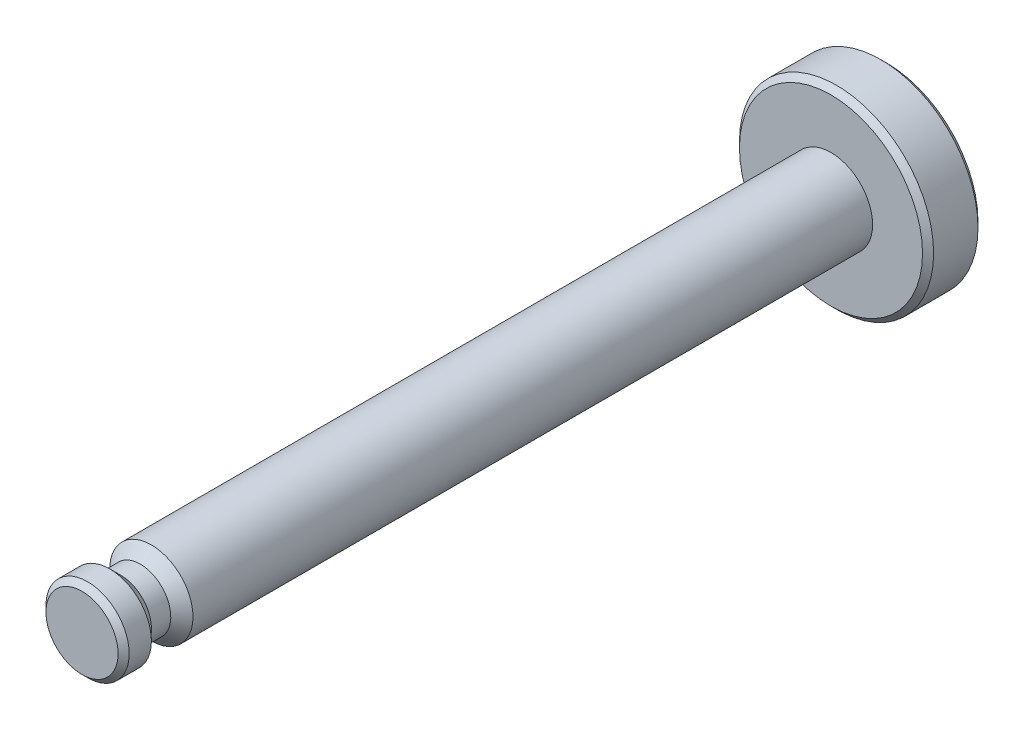
SolidWorks part; units mm, degrees
ref_plane "Front" through (0, 0, 0) normal (0, 0, 1) x (1, 0, 0)
ref_plane "Top" through (0, 0, 0) normal (0, 1, 0) x (1, 0, 0)
ref_plane "Right" through (0, 0, 0) normal (1, 0, 0) x (0, 0, -1)
sketch "Sketch2" plane through (0, 0, 0) normal (0, 0, 1) x (1, 0, 0)
  circle A0 centre (0, 0) radius 1.5
  dimension "D1" = 3
extrude "Shaft" add sketch "Sketch2" along normal blind 27
sketch "Sketch3" plane through (0, 0, 0) normal (0, 0, -1) x (-1, 0, 0)
  circle A3 centre (0, 0) radius 3.5
  dimension "D1" = 7
extrude "Head" add sketch "Sketch3" along normal blind 2
sketch "Sketch4" plane through (0, 0, 0) normal (1, 0, 0) x (0, 0, -1)
  line L0 (0, 0) -> (-25.25, 0) construction
  line L1 (-25.25, 0) -> (-25.25, 4.3666) construction
  line L2 (-26, 1.5) -> (-24.5, 1.5)
  line L3 (0, 1.5) -> (-27, 1.5) construction
  line L6 (-24.5, 1.5) -> (-24.9, 1.1)
  line L7 (-24.9, 1.1) -> (-25.6, 1.1)
  line L8 (-25.6, 1.1) -> (-26, 1.5)
  dimension "D1" = 25.25
  dimension "D2" = 1.5
  dimension "D3" = 45
  dimension "D4" = 0.4
revolve "e-Clip Notch" cut sketch "Sketch4" angle 360 about L0
chamfer "Deburs" distance 0.2 angle 45 3 edges at (1.5, 0, 27) (-3.5, 0, 0) (-3.5, 0, -2)
equation "\"D1@Shaft\"=\"Hardware Length@Box Assy.Assembly\"+7mm"
equation "\"D1@Sketch4\"=\"Hardware Length@Box Assy.Assembly\" + 5.25mm"
equation "\"D1@Sketch2\"=\"Hardware Clearance Hole Diameter@Box Assy.Assembly\"-.15"
